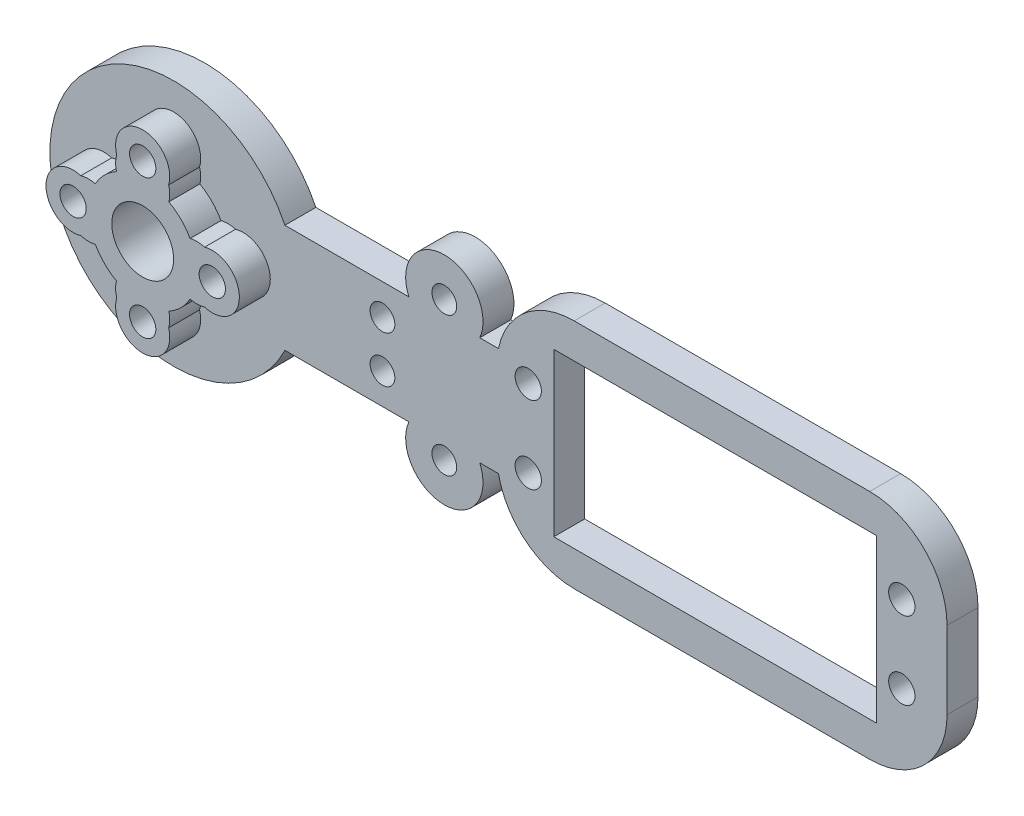
SolidWorks part; units mm, degrees
ref_plane "Front Plane" through (0, 0, 0) normal (0, 0, 1) x (1, 0, 0)
ref_plane "Top Plane" through (0, 0, 0) normal (0, 1, 0) x (1, 0, 0)
ref_plane "Right Plane" through (0, 0, 0) normal (1, 0, 0) x (0, 0, -1)
sketch "Main_web_profile" plane through (0, 0, 0) normal (0, 0, 1) x (1, 0, 0)
  line L1 (0, -7) -> (60, -7)
  line L2 (0, -7) -> (0, 7)
  line L3 (0, 7) -> (60, 7)
  line L4 (60, -7) -> (60, 7)
  dimension "D1" = 60
  dimension "D2" = 14
  dimension "D3" = 7
extrude "Main_web" add sketch "Main_web_profile" along normal blind 4
sketch "Shoulder_horn_flange_profile" plane through (0, 0, 0) normal (0, 0, 1) x (1, 0, 0)
  circle A0 centre (0, 0) radius 16
  dimension "D1" = 32
extrude "Shoulder_horn_flange" add sketch "Shoulder_horn_flange_profile" along normal blind 4
sketch "Elbow_servo_mount_profile" plane through (0, 0, 0) normal (0, 0, 1) x (1, 0, 0)
  line L1 (42, -14) -> (90, -14)
  line L2 (42, -14) -> (42, 14)
  line L3 (42, 14) -> (90, 14)
  line L4 (90, -14) -> (90, 14)
  dimension "D1" = 48
  dimension "D2" = 28
  dimension "D3" = 42
  dimension "D4" = 14
extrude "Elbow_servo_mount" add sketch "Elbow_servo_mount_profile" along normal blind 4
sketch "SG90_body_clearance_profile" plane through (0, 0, 0) normal (0, 0, 1) x (1, 0, 0)
  line L1 (53.6, -6.5) -> (77.4, -6.5)
  line L2 (53.6, -6.5) -> (53.6, 6.5)
  line L3 (53.6, 6.5) -> (77.4, 6.5)
  line L4 (77.4, -6.5) -> (77.4, 6.5)
  dimension "D1" = 23.8
  dimension "D2" = 13
  dimension "D3" = 53.6
  dimension "D4" = 6.5
extrude "SG90_body_clearance" cut sketch "SG90_body_clearance_profile" along normal through all from offset 5 offset against normal yes
sketch "Elbow_tab_fasteners_profile" plane through (0, 0, 0) normal (0, 0, 1) x (1, 0, 0)
  circle A0 centre (51, 0) radius 1.3
  circle A1 centre (80, 0) radius 1.3
  dimension "D1" = 2.6
  dimension "D2" = 2.6
  dimension "D3" = 51
  dimension "D4" = 80
extrude "Elbow_tab_fasteners" cut sketch "Elbow_tab_fasteners_profile" along normal through all from offset 50 offset against normal yes
sketch "Shoulder_center_screw_access_profile" plane through (0, 0, 0) normal (0, 0, 1) x (1, 0, 0)
  circle A0 centre (0, 0) radius 4
  dimension "D1" = 8
extrude "Shoulder_center_screw_access" cut sketch "Shoulder_center_screw_access_profile" along normal through all from offset 50 offset against normal yes
sketch "Cable_tie_holes_profile" plane through (0, 0, 0) normal (0, 0, 1) x (1, 0, 0)
  circle A0 centre (27, -3) radius 1.6
  circle A1 centre (27, 3) radius 1.6
  dimension "D1" = 3.2
  dimension "D2" = 3.2
  dimension "D3" = 27
  dimension "D4" = 3
  dimension "D5" = 3
extrude "Cable_tie_holes" cut sketch "Cable_tie_holes_profile" along normal through all from offset 50 offset against normal yes
sketch "Passive_lower_mount_boss_profile" plane through (0, 0, 0) normal (0, 0, 1) x (1, 0, 0)
  circle A0 centre (35, -9) radius 5
  dimension "D1" = 10
  dimension "D2" = 35
  dimension "D3" = 9
extrude "Passive_lower_mount_boss" add sketch "Passive_lower_mount_boss_profile" along normal blind 4
sketch "Passive_upper_mount_boss_profile" plane through (0, 0, 0) normal (0, 0, 1) x (1, 0, 0)
  circle A0 centre (35, 9) radius 5
  dimension "D1" = 10
  dimension "D2" = 35
  dimension "D3" = 9
extrude "Passive_upper_mount_boss" add sketch "Passive_upper_mount_boss_profile" along normal blind 4
sketch "Passive_cheek_standoffs_profile" plane through (0, 0, 0) normal (0, 0, 1) x (1, 0, 0)
  circle A0 centre (35, -9) radius 1.6
  circle A1 centre (35, 9) radius 1.6
  dimension "D1" = 3.2
  dimension "D2" = 3.2
  dimension "D3" = 35
  dimension "D4" = 9
  dimension "D5" = 9
extrude "Passive_cheek_standoffs" cut sketch "Passive_cheek_standoffs_profile" along normal through all from offset 50 offset against normal yes
sketch "Shoulder_dowel_support_hub_profile" plane through (0, 0, 0) normal (0, 0, 1) x (1, 0, 0)
  circle A0 centre (0, 0) radius 7
  circle A1 centre (0, 0) radius 4
  dimension "D1" = 14
  dimension "D2" = 8
extrude "Shoulder_dowel_support_hub" add sketch "Shoulder_dowel_support_hub_profile" along normal blind 4 from offset 4
sketch "Raised_M3_washer_seats_PCD14_profile" plane through (0, 0, 0) normal (0, 0, 1) x (1, 0, 0)
  circle A0 centre (7, 0) radius 3.5
  circle A1 centre (-7, 0) radius 3.5
  circle A2 centre (0, 7) radius 3.5
  circle A3 centre (0, -7) radius 3.5
  dimension "D1" = 7
  dimension "D2" = 7
  dimension "D3" = 7
  dimension "D4" = 7
  dimension "D5" = 7
  dimension "D6" = 7
  dimension "D7" = 7
  dimension "D8" = 7
extrude "Raised_M3_washer_seats_height8" add sketch "Raised_M3_washer_seats_PCD14_profile" along normal blind 4 from offset 4
sketch "Metal_horn_M3_clearance_PCD14_profile" plane through (0, 0, 0) normal (0, 0, 1) x (1, 0, 0)
  circle A0 centre (7, 0) radius 1.6
  circle A1 centre (-7, 0) radius 1.6
  circle A2 centre (0, 7) radius 1.6
  circle A3 centre (0, -7) radius 1.6
  dimension "D1" = 3.2
  dimension "D2" = 3.2
  dimension "D3" = 3.2
  dimension "D4" = 3.2
  dimension "D5" = 7
  dimension "D6" = 7
  dimension "D7" = 7
  dimension "D8" = 7
extrude "Metal_horn_M3_clearance_PCD14_SUPERSEDED_owned_servo" [suppressed] cut sketch "Metal_horn_M3_clearance_PCD14_profile" along normal through all from offset 50 offset against normal yes
sketch "Restore_shoulder_sleeve_bore_profile" plane through (0, 0, 0) normal (0, 0, 1) x (1, 0, 0)
  circle A0 centre (0, 0) radius 4
  dimension "D1" = 8
extrude "Restore_shoulder_sleeve_bore" cut sketch "Restore_shoulder_sleeve_bore_profile" along normal through all from offset 50 offset against normal yes
fillet "Fillet1" radius 7.5 4 edges at (42, -14, 2) (90, -14, 2) (90, 14, 2) (42, 14, 2)
sketch "Larger_elbow_servo_mount_replaces_SG90_opening_profile" plane through (0, 0, 0) normal (0, 0, 1) x (1, 0, 0)
  line L1 (42, -15) -> (100, -15)
  line L2 (42, -15) -> (42, 15)
  line L3 (42, 15) -> (100, 15)
  line L4 (100, -15) -> (100, 15)
  dimension "D1" = 58
  dimension "D2" = 30
  dimension "D3" = 42
  dimension "D4" = 15
extrude "Larger_elbow_servo_mount_replaces_SG90_opening" add sketch "Larger_elbow_servo_mount_replaces_SG90_opening_profile" along normal blind 4
sketch "MG996R_elbow_body_clearance_profile" plane through (0, 0, 0) normal (0, 0, 1) x (1, 0, 0)
  line L1 (49.5, -10.35) -> (91.2, -10.35)
  line L2 (49.5, -10.35) -> (49.5, 10.35)
  line L3 (49.5, 10.35) -> (91.2, 10.35)
  line L4 (91.2, -10.35) -> (91.2, 10.35)
  dimension "D1" = 41.7
  dimension "D2" = 20.7
  dimension "D3" = 49.5
  dimension "D4" = 10.35
extrude "MG996R_elbow_body_clearance_SUPERSEDED_owned_servo" [suppressed] cut sketch "MG996R_elbow_body_clearance_profile" along normal through all from offset 5 offset against normal yes
sketch "MG996R_elbow_tab_fasteners_profile" plane through (0, 0, 0) normal (0, 0, 1) x (1, 0, 0)
  circle A0 centre (47, -5) radius 1.5
  circle A1 centre (47, 5) radius 1.5
  circle A2 centre (94, -5) radius 1.5
  circle A3 centre (94, 5) radius 1.5
  dimension "D1" = 3
  dimension "D2" = 3
  dimension "D3" = 3
  dimension "D4" = 3
  dimension "D5" = 47
  dimension "D6" = 94
  dimension "D7" = 5
  dimension "D8" = 5
extrude "MG996R_elbow_tab_fasteners_SUPERSEDED_owned_servo" [suppressed] cut sketch "MG996R_elbow_tab_fasteners_profile" along normal through all from offset 50 offset against normal yes
fillet "Fillet2" radius 10 4 edges at (42, 15, 2) (42, -15, 2) (100, -15, 2) (100, 15, 2)
sketch "Owned_MG996R_elbow_body_window_profile" plane through (0, 0, 0) normal (0, 0, 1) x (1, 0, 0)
  line L1 (49.151, -10.5) -> (90.849, -10.5)
  line L2 (49.151, -10.5) -> (49.151, 10.5)
  line L3 (49.151, 10.5) -> (90.849, 10.5)
  line L4 (90.849, -10.5) -> (90.849, 10.5)
  dimension "D1" = 41.698
  dimension "D2" = 21
  dimension "D3" = 49.151
  dimension "D4" = 10.5
extrude "Owned_MG996R_elbow_body_window" cut sketch "Owned_MG996R_elbow_body_window_profile" along normal through all from offset 5 offset against normal yes
sketch "Owned_MG996R_elbow_M3_ear_holes_profile" plane through (0, 0, 0) normal (0, 0, 1) x (1, 0, 0)
  circle A0 centre (45.85, -5) radius 1.7
  circle A1 centre (45.85, 5) radius 1.7
  circle A2 centre (94.15, -5) radius 1.7
  circle A3 centre (94.15, 5) radius 1.7
  dimension "D1" = 3.4
  dimension "D2" = 3.4
  dimension "D3" = 3.4
  dimension "D4" = 3.4
  dimension "D5" = 45.85
  dimension "D6" = 94.15
  dimension "D7" = 5
  dimension "D8" = 5
extrude "Owned_MG996R_elbow_M3_ear_holes" cut sketch "Owned_MG996R_elbow_M3_ear_holes_profile" along normal through all from offset 50 offset against normal yes
sketch "Printed_hub_washer_seats_PCD18_profile" plane through (0, 0, 0) normal (0, 0, 1) x (1, 0, 0)
  circle A0 centre (9, 0) radius 3.5
  circle A1 centre (0, 9) radius 3.5
  circle A2 centre (-9, 0) radius 3.5
  circle A3 centre (0, -9) radius 3.5
  dimension "D1" = 7
  dimension "D2" = 7
  dimension "D3" = 7
  dimension "D4" = 7
  dimension "D5" = 9
  dimension "D6" = 9
  dimension "D7" = 9
  dimension "D8" = 9
extrude "Printed_hub_M3_washer_seats_PCD18" add sketch "Printed_hub_washer_seats_PCD18_profile" along normal blind 4 from offset 4
sketch "Printed_hub_M3_clearance_PCD18_profile" plane through (0, 0, 0) normal (0, 0, 1) x (1, 0, 0)
  circle A0 centre (9, 0) radius 1.7
  circle A1 centre (0, 9) radius 1.7
  circle A2 centre (-9, 0) radius 1.7
  circle A3 centre (0, -9) radius 1.7
  dimension "D1" = 3.4
  dimension "D2" = 3.4
  dimension "D3" = 3.4
  dimension "D4" = 3.4
  dimension "D5" = 9
  dimension "D6" = 9
  dimension "D7" = 9
  dimension "D8" = 9
extrude "Printed_hub_M3_clearance_PCD18" cut sketch "Printed_hub_M3_clearance_PCD18_profile" along normal through all from offset 50 offset against normal yes
